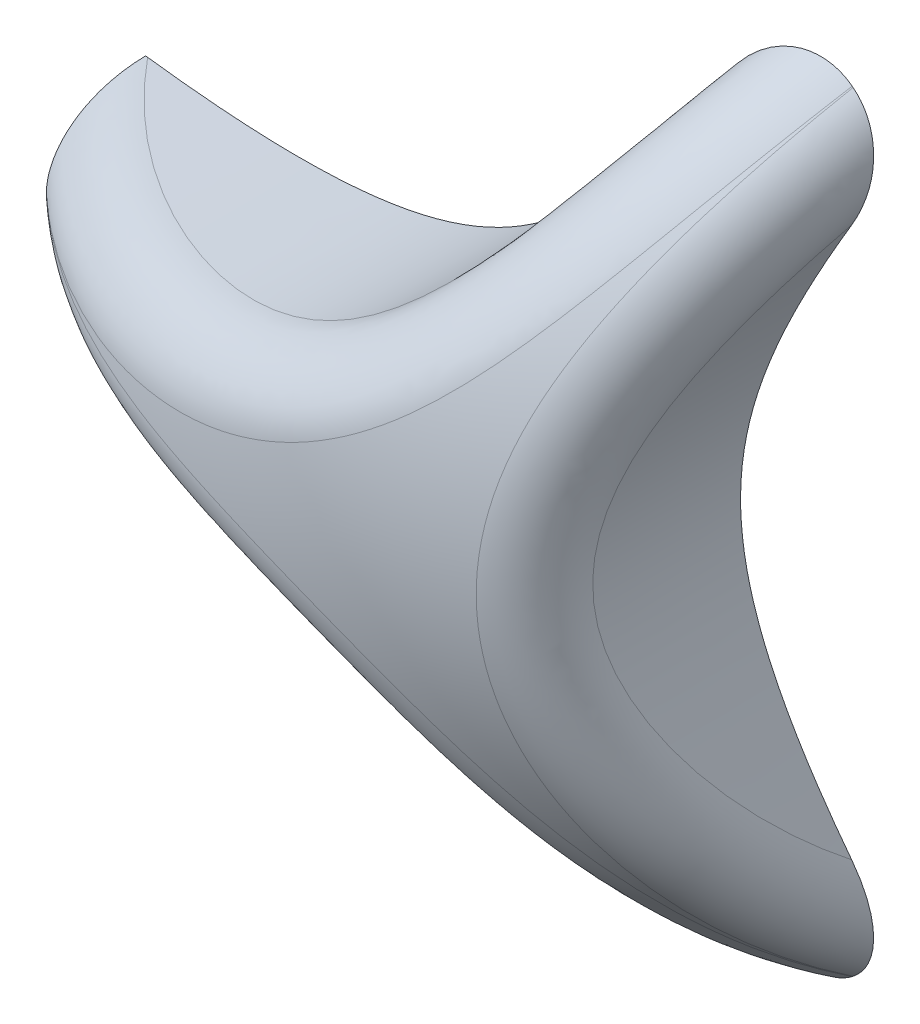
SolidWorks part; units mm, degrees
ref_plane "Front Plane" through (0, 0, 0) normal (0, 0, 1) x (1, 0, 0)
ref_plane "Top Plane" through (0, 0, 0) normal (0, 1, 0) x (1, 0, 0)
ref_plane "Right Plane" through (0, 0, 0) normal (1, 0, 0) x (0, 0, -1)
sketch "Sketch1" plane through (0, 0, 0) normal (0, 0, 1) x (1, 0, 0)
  line L0 (6.299, 7.9103) -> (3.701, 9.4103)
  line L1 (-10, 1.5) -> (0, 1.5) construction
  line L2 (-10, 1.5) -> (-10, -1.5)
  line L3 (-10, -1.5) -> (0, -1.5) construction
  line L4 (0, 1.5) -> (0, -1.5) construction
  line L5 (6.299, 7.9103) -> (1.299, -0.75) construction
  line L6 (3.701, 9.4103) -> (-1.299, 0.75) construction
  line L7 (1.299, -0.75) -> (-1.299, 0.75) construction
  line L8 (3.701, -9.4103) -> (6.299, -7.9103)
  line L9 (3.701, -9.4103) -> (-1.299, -0.75) construction
  line L10 (6.299, -7.9103) -> (1.299, 0.75) construction
  line L11 (-1.299, -0.75) -> (1.299, 0.75) construction
  spline S0 degree 3 poles (-10, 1.5) (-1.6667, 1.5) (-0.4657, 2.1934) (3.701, 9.4103) knots 0 0 0 0 1 1 1 1
  spline S1 degree 3 poles (6.299, 7.9103) (2.1324, 0.6934) (2.1324, -0.6934) (6.299, -7.9103) knots 0 0 0 0 1 1 1 1
  spline S2 degree 3 poles (3.701, -9.4103) (-0.4657, -2.1934) (-1.6667, -1.5) (-10, -1.5) knots 0 0 0 0 1 1 1 1
  point P4 (0, 0)
  point P16 (0, 0)
  point P21 (0, 0)
  dimension "D4" = 25
  dimension "D5" = 25
  dimension "D1" = 3
  dimension "D2" = 10
  dimension "D3" = 3
extrude "Boss-Extrude1" add sketch "Sketch1" along normal mid plane 15 from offset 75
sketch "Sketch2" plane through (0, 0, 0) normal (0, 1, 0) x (1, 0, 0)
  line L0 (-1.4683, -71.4755) -> (-1.4683, -76.4755)
  arc A0 (-11.9831, -70.7348) -> (-1.4683, -71.4755) centre (-1.4683, 3.5245) ccw
  arc A1 (-11.9831, -70.7348) -> (-1.4683, -76.4755) centre (-1.4683, -63.9755) ccw
  dimension "D1" = 25
  dimension "150" = 150
  dimension "D2" = 5
revolve "Revolve2" add sketch "Sketch2" angle 360 about L0
combine bodies "Combine1" operation type common bodies to combine 101 103
fillet "Fillet1" radius 1.5 3 edges at (-2.0603, -2.5002, 76.2086) (-1.4851, 2.8088, 76.1559) (3.2419, -0.9552, 75.5147)
sketch "Sketch3" plane through (0, 0, 0) normal (0, 0, 1) x (1, 0, 0)
  line L0 (0, 0) -> (10.9199, 5.5579) construction
